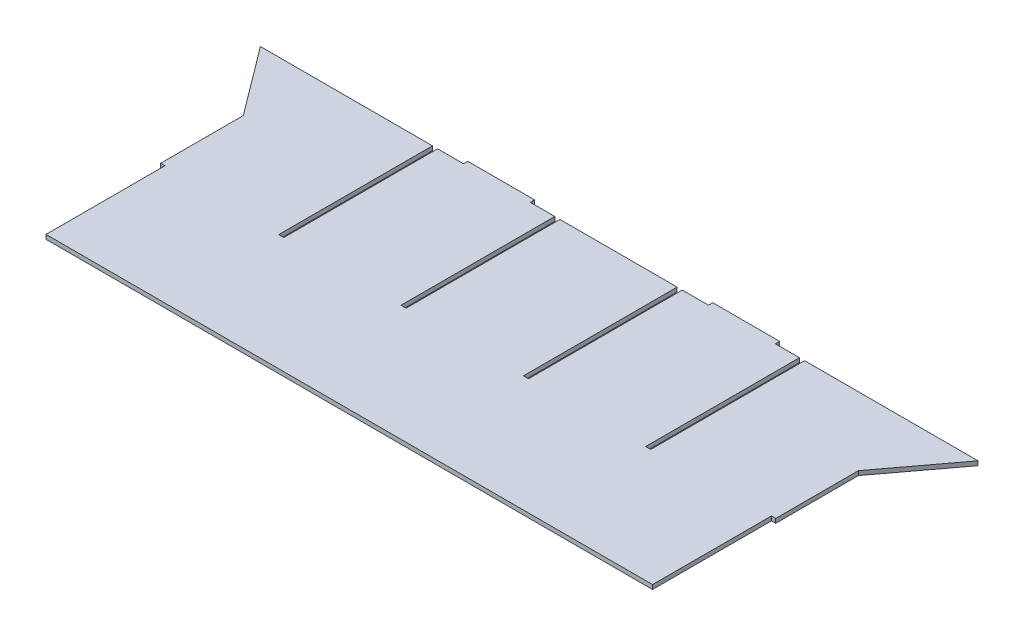
SolidWorks part; units mm, degrees
material "6061-T6 (SS)"
ref_plane "X-Y Datum" through (0, 0, 0) normal (0, 0, 1) x (1, 0, 0)
ref_plane "X-Z Datum" through (0, 0, 0) normal (0, 1, 0) x (1, 0, 0)
ref_plane "Y-Z Datum" through (0, 0, 0) normal (1, 0, 0) x (0, 0, -1)
sketch "Sketch1" plane through (0, 0, 0) normal (0, 0, 1) x (1, 0, 0)
  line L1 (-228.601, -1.5875) -> (228.601, -1.5875)
  line L2 (-228.601, -1.5875) -> (-228.601, 1.5875)
  line L3 (-228.601, 1.5875) -> (228.601, 1.5875)
  line L4 (228.601, -1.5875) -> (228.601, 1.5875)
  line L5 (-228.601, -1.5875) -> (228.601, 1.5875) construction
  line L6 (-228.601, 1.5875) -> (228.601, -1.5875) construction
  point P0 (0, 0)
  dimension "D1" = 3.175
  dimension "D2" = 457.202
extrude "Boss-Extrude1" add sketch "Sketch1" along normal blind 200.642
sketch "Sketch2" plane through (0, 1.5875, 0) normal (0, 1, 0) x (1, 0, 0)
  line L0 (228.601, 0) -> (225.426, 0)
  line L1 (228.601, 0) -> (-228.601, 0) construction
  line L2 (225.426, 0) -> (137.796, 0)
  line L3 (137.796, 0) -> (133.986, 0)
  line L10 (133.986, 0) -> (137.796, 0)
  line L11 (133.986, 0) -> (133.986, -114.3)
  line L12 (133.986, -114.3) -> (137.796, -114.3)
  line L13 (137.796, 0) -> (137.796, -114.3)
  line M2 (228.601, 0) -> (-228.601, 0)
  dimension "D1" = 87.63
  dimension "D2" = 3.175
  dimension "D3" = 114.3
extrude "Cut-Extrude1" cut sketch "Sketch2" against normal through all contours L13 L11 L12 M2 region at (135.891, 1.5875, 57.15)
pattern_linear "LPattern1" count 4 spacing 90.932 along (-1, 0, 0) of "Cut-Extrude1"
sketch "Sketch3" plane through (0, 0, 0) normal (0, 0, -1) x (-1, 0, 0)
  line L1 (-66.3072, 1.5875) -> (-115.966, 1.5875)
  line L2 (-66.3072, 1.5875) -> (-66.3072, -1.5875)
  line L3 (-66.3072, -1.5875) -> (-115.966, -1.5875)
  line L4 (-115.966, 1.5875) -> (-115.966, -1.5875)
  line L5 (66.0742, 1.5875) -> (115.733, 1.5875)
  line L6 (66.0742, 1.5875) -> (66.0742, -1.5875)
  line L7 (66.0742, -1.5875) -> (115.733, -1.5875)
  line L8 (115.733, 1.5875) -> (115.733, -1.5875)
sketch "Sketch4" plane through (0, -1.5875, 0) normal (0, -1, 0) x (1, 0, 0)
  line L0 (-228.601, 0) -> (-266.701, 0)
  line L1 (-266.701, 0) -> (-228.601, 50.8)
  line L2 (-228.601, 200.642) -> (-228.601, 0) construction
  line L3 (-228.601, 50.8) -> (-228.601, 0)
  dimension "D1" = 38.1
  dimension "D2" = 50.8
extrude "Boss-Extrude3" add sketch "Sketch4" against normal blind 3.175
mirror "Mirror1" about plane through (0, 0, 0) normal (1, 0, 0) of "Boss-Extrude3"
sketch "Sketch5" plane through (0, -1.5875, 0) normal (0, -1, 0) x (1, 0, 0)
  line L1 (-228.601, 200.642) -> (-225.426, 200.642)
  line L2 (-228.601, 200.642) -> (-228.601, 112.25)
  line L3 (-228.601, 112.25) -> (-225.426, 112.25)
  line L4 (-225.426, 200.642) -> (-225.426, 112.25)
  dimension "D1" = 3.175
  dimension "D2" = 88.392
extrude "Cut-Extrude2" cut sketch "Sketch5" against normal blind 3.175
mirror "Mirror2" about plane through (0, 0, 0) normal (1, 0, 0) of "Cut-Extrude2"
extrude "Boss-Extrude4" add sketch "Sketch3" along normal blind 3.175
